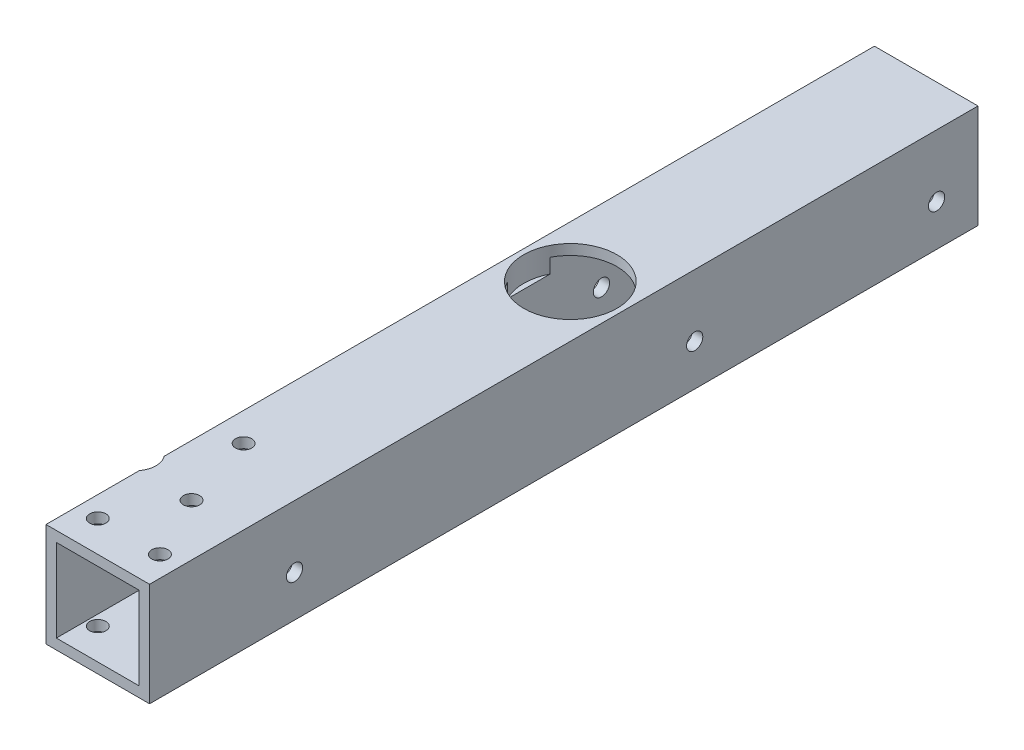
SolidWorks part; units mm, degrees
material "6061 Alloy"
ref_plane "Front Plane" through (0, 0, 0) normal (0, 0, 1) x (1, 0, 0)
ref_plane "Top Plane" through (0, 0, 0) normal (0, 1, 0) x (1, 0, 0)
ref_plane "Right Plane" through (0, 0, 0) normal (1, 0, 0) x (0, 0, -1)
sketch "Sketch1" plane through (0, 0, 0) normal (0, 0, 1) x (1, 0, 0)
  line L0 (-12.7, 12.7) -> (12.7, 12.7)
  line L2 (-15.875, 15.875) -> (15.875, 15.875)
  line L3 (-15.875, 15.875) -> (-15.875, -15.875)
  line L4 (-15.875, -15.875) -> (15.875, -15.875)
  line L5 (15.875, 15.875) -> (15.875, -15.875)
  line L10 (12.7, 12.7) -> (12.7, -12.7)
  line L11 (-12.7, -12.7) -> (12.7, -12.7)
  line L12 (-12.7, 12.7) -> (-12.7, -12.7)
  point P12 (0, 15.875)
  point P14 (15.875, 0)
  dimension "Wall Thickness" = 3.175
  dimension "Outside Width" = 31.75
  dimension "Outside Height" = 31.75
  dimension "Inside Height" = 25.4
  dimension "Inside Width" = 25.4
sketch "Sketch2" plane through (0, 0, 0) normal (1, 0, 0) x (0, 0, -1)
  line L0 (127, 0) -> (-127, 0)
  point P4 (0, 0)
  point P7 (-127, 0)
  point P10 (127, 0)
  dimension "Length" = 254
sketch "Sketch3" plane through (0, 0, 0) normal (0, 0, 1) x (1, 0, 0)
  line L21 (15.875, 15.875) -> (-15.875, 15.875)
  line L22 (15.875, -15.875) -> (15.875, 15.875)
  line L23 (-15.875, -15.875) -> (15.875, -15.875)
  line L24 (-15.875, 15.875) -> (-15.875, -15.875)
  line L25 (15.875, 15.875) -> (-15.875, 15.875)
  line L26 (15.875, -15.875) -> (15.875, 15.875)
  line L27 (-15.875, -15.875) -> (15.875, -15.875)
  line L28 (-15.875, 15.875) -> (-15.875, -15.875)
  line L29 (12.7, 12.7) -> (-12.7, 12.7)
  line L30 (12.7, -12.7) -> (12.7, 12.7)
  line L31 (-12.7, -12.7) -> (12.7, -12.7)
  line L32 (-12.7, 12.7) -> (-12.7, -12.7)
  line L33 (12.7, 12.7) -> (-12.7, 12.7)
  line L34 (12.7, -12.7) -> (12.7, 12.7)
  line L35 (-12.7, -12.7) -> (12.7, -12.7)
  line L36 (-12.7, 12.7) -> (-12.7, -12.7)
  dimension "D1" = 0
  dimension "D2" = 0
extrude "Boss-Extrude1" add sketch "Sketch3" along normal up to vertex (127 mm away) and the other way up to vertex (127 mm away) up to point (0, 0, 127) other way up to point (0, 0, -127)
sketch "Drawing Reference" plane through (0, 0, 0) normal (1, 0, 0) x (0, 0, -1)
  line L0 (-127, 0) -> (127, 0) construction
  line L1 (0, -15.875) -> (0, 15.875) construction
  line L2 (-127, -15.875) -> (127, -15.875) construction
  line L5 (-127, 15.875) -> (127, 15.875) construction
  point P7 (-104.14, 0)
  point P8 (104.14, 0)
  dimension "D1" = 22.86
sketch "Sketch4" plane through (0, 15.875, 0) normal (0, 1, 0) x (1, 0, 0)
  line L0 (0, -127) -> (0, -117.475) construction
  line L1 (15.875, -127) -> (-15.875, -127) construction
  line L2 (0, -117.475) -> (9.525, -117.475) construction
  line L3 (0, -117.475) -> (-9.525, -117.475) construction
  line L4 (0, -117.475) -> (0, 17.8816) construction
  line L5 (0, -117.475) -> (0, -98.2472) construction
  point P5 (-7.1119, -75.1713)
  dimension "D1" = 135.3566
  dimension "D2" = 19.05
  dimension "D3" = 9.525
hole_wizard "#10 Clearance Hole1" positions "Sketch5" profile "Sketch6" hole size "#10" standard "ANSI Inch" end condition through all
sketch "Sketch5" plane through (0, 15.875, 0) normal (0, 1, 0) x (1, 0, 0)
  point P0 (-9.525, -117.475)
  point P3 (9.525, -117.475)
  point P7 (0, -98.2472)
  point P10 (-7.1119, -75.1713)
sketch "Sketch6" plane through (-9.525, 15.875, 117.475) normal (1, 0, 0) x (0, 0, 1)
  line L0 (0, 0) -> (0, 31.75)
  line L1 (0, 31.75) -> (2.4892, 31.75)
  line L2 (2.4892, 31.75) -> (2.4892, 0)
  line L5 (2.4892, 0) -> (0, 0)
  line L11 (0, -6.35) -> (0, 107.95) construction
  dimension "Thru Hole Dia." = 4.9784
  dimension "Thru Hole Depth" = 31.75
sketch "Sketch7" plane through (0, 15.875, 0) normal (0, 1, 0) x (1, 0, 0)
  circle A0 centre (0, 17.8816) radius 14.2875
  dimension "D1" = 28.575
extrude "Cut-Extrude1" cut sketch "Sketch7" against normal blind 7.62
sketch "Sketch8" plane through (0, -15.875, 0) normal (0, -1, 0) x (1, 0, 0)
  circle A0 centre (0, -17.8816) radius 14.2875
  dimension "D1" = 28.575
extrude "Cut-Extrude2" cut sketch "Sketch8" against normal blind 7.62
sketch "Sketch9" plane through (15.875, 0, 0) normal (1, 0, 0) x (0, 0, -1)
  line L0 (-127, -3.175) -> (-82.55, -3.175) construction
  line L2 (-82.55, -3.175) -> (114.3, -3.175) construction
  line L3 (-127, 15.875) -> (-127, -3.175) construction
  line L4 (52.832, -3.175) -> (40.132, -3.175) construction
  line L5 (52.832, 10.4775) -> (52.832, -434.0225) construction
  dimension "D1" = 44.45
  dimension "D2" = 19.05
  dimension "D3" = 12.7
hole_wizard "#10 Clearance Hole2" positions "Sketch10" profile "Sketch11" hole size "#10" standard "ANSI Inch" end condition through all
sketch "Sketch10" plane through (15.875, 0, 0) normal (1, 0, 0) x (0, 0, -1)
  point P0 (-82.55, -3.175)
  point P4 (114.3, -3.175)
  point P8 (40.132, -3.175)
sketch "Sketch11" plane through (15.875, -3.175, 82.55) normal (0, 1, 0) x (0, 0, -1)
  line L0 (0, 0) -> (0, 31.75)
  line L1 (0, 31.75) -> (2.4892, 31.75)
  line L2 (2.4892, 31.75) -> (2.4892, 0)
  line L5 (2.4892, 0) -> (0, 0)
  line L11 (0, -6.35) -> (0, 107.95) construction
  dimension "Thru Hole Dia." = 4.9784
  dimension "Thru Hole Depth" = 31.75
sketch "Sketch12" plane through (0, 15.875, 0) normal (0, 1, 0) x (1, 0, 0)
  line L0 (-20.955, -94.5576) -> (-15.875, -94.5576) construction
  line L1 (-15.875, -127) -> (-15.875, 127) construction
  circle A0 centre (-20.955, -94.5576) radius 6.35
  dimension "D1" = 5.08
extrude "Cut-Extrude3" cut sketch "Sketch12" against normal through all
sketch "Sketch13" plane through (0, -15.875, 0) normal (0, -1, 0) x (1, 0, 0)
  line L0 (0, 0.1524) -> (0, -35.9156) construction
  line L1 (0, -17.8816) -> (3.2229, -17.8816) construction
  point P8 (0, -17.8816)
  dimension "D1" = 36.068
hole_wizard "Tap Drill for #10-32 Tap1" positions "Sketch14" profile "Sketch15" hole size "#10-32" standard "ANSI Inch"
sketch "Sketch14" plane through (0, -15.875, 0) normal (0, -1, 0) x (-1, 0, 0)
  point P2 (0, 35.9156)
  point P5 (0, -0.1524)
sketch "Sketch15" plane through (0, -15.875, -35.9156) normal (1, 0, 0) x (0, 0, -1)
  line L0 (0, 0) -> (0, 6.2933)
  line L1 (0, 6.2933) -> (2.0193, 5.08)
  line L2 (2.0193, 5.08) -> (2.0193, 0)
  line L5 (2.0193, 0) -> (0, 0)
  line L10 (0, 6.2933) -> (-2.0193, 5.08) construction
  line L11 (0, -6.35) -> (0, 107.95) construction
  dimension "Hole Dia." = 4.0386
  dimension "Hole Depth" = 5.08
  dimension "Drill Angle" = 118
equation "\"D1@Drawing Reference\"=\"Outside Width@Sketch1\" * 0.72"
